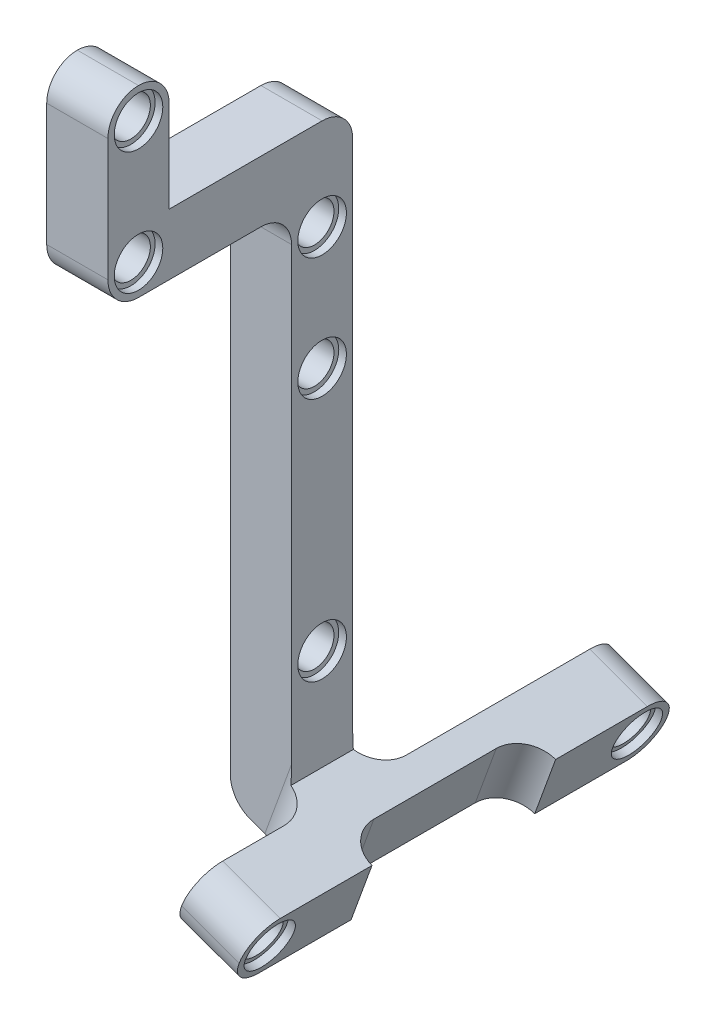
SolidWorks part; units mm, degrees
ref_plane "Front Plane" through (0, 0, 0) normal (1, 0, 0) x (0, 1, 0)
ref_plane "Top Plane" through (0, 0, 0) normal (0, 0, 1) x (0, 1, 0)
ref_plane "Right Plane" through (0, 0, 0) normal (0, 1, 0) x (-1, 0, 0)
sketch "Sketch1" plane through (0, 0, 0) normal (1, 0, 0) x (0, 1, 0)
  line L0 (72, 0) -> (72, 24)
  line L1 (0, 0) -> (72, 0)
  line L2 (0, 0) -> (0, 32)
  line L3 (0, 32) -> (64, 32)
  line L5 (0, 32) -> (64, 32)
  line L6 (0, 32) -> (0, 8)
  line L7 (0, 8) -> (64, 8)
  line L8 (64, 32) -> (64, 8)
  line L9 (64, 32) -> (88, 32)
  line L11 (72, 24) -> (88, 24)
  line L12 (88, 32) -> (88, 24)
  circle A4 centre (68, 28) radius 2.55
  circle A6 centre (84, 28) radius 2.55
  circle A7 centre (12, 4) radius 2.55
  circle A8 centre (44, 4) radius 2.55
  circle A9 centre (60, 4) radius 2.55
  dimension "D5" = 32
  dimension "D14" = 12
  dimension "D15" = 4
  dimension "D16" = 24
  dimension "D17" = 4
  dimension "D19" = 5.1
  dimension "D10" = 5.1
  dimension "D7" = 5.1
  dimension "D9" = 5.1
  dimension "D2" = 8
  dimension "D3" = 24
  dimension "D4" = 64
  dimension "D6" = 16
  dimension "D8" = 32
  dimension "D11" = 16
  dimension "D12" = 4
  dimension "D13" = 4
  dimension "D18" = 8
  dimension "24" = 24
  dimension "D20" = 16
  dimension "D21" = 4
  dimension "D22" = 4
extrude "Boss-Extrude1" add sketch "Sketch1" along normal blind 8 contours L3 L8 L7 L2 L1 region at (0, 36, 0.9364)
sketch "Sketch2" plane through (8, 0, 0) normal (1, 0, 0) x (0, 1, 0)
  circle A0 centre (68, 28) radius 3.175
  circle A7 centre (84, 28) radius 3.175
  circle A8 centre (12, 4) radius 3.175
  circle A9 centre (44, 4) radius 3.175
  circle A10 centre (60, 4) radius 3.175
  dimension "D1" = 6.35
extrude "Cut-Extrude1" cut sketch "Sketch2" against normal blind 1
sketch "Sketch3" plane through (0, 0, 0) normal (-1, 0, 0) x (0, -1, 0)
  circle A3 centre (-12, 4) radius 3.175
  circle A5 centre (-12, 4) radius 3.175
  circle A7 centre (-84, 28) radius 3.175
  circle A23 centre (-84, 28) radius 3.175
  circle A28 centre (-68, 28) radius 3.175
  circle A29 centre (-68, 28) radius 3.175
  circle A40 centre (-60, 4) radius 3.175
  circle A41 centre (-60, 4) radius 3.175
  circle A42 centre (-44, 4) radius 3.175
  circle A43 centre (-44, 4) radius 3.175
  dimension "D5" = 0
  dimension "D1" = 0
  dimension "D2" = 0
  dimension "D11" = 0
  dimension "D12" = 0
extrude "Cut-Extrude2" cut sketch "Sketch3" against normal blind 1
sketch "Sketch4" plane through (0, 0, 8) normal (0, 0, 1) x (1, 0, 0)
  line L0 (8, 0) -> (0, 0) construction
  line L1 (8, 0) -> (8, 64) construction
  line L2 (0, 0) -> (0, -4)
  line L3 (0, 0) -> (0, 64) construction
  line L4 (15.7876, -12.5471) -> (18.5238, -5.0295)
  line L5 (8, -1.1992) -> (18.5238, -5.0295)
  line L6 (15.7876, -12.5471) -> (2.6319, -7.7588)
  line L7 (8, 0) -> (8, -1.1992)
  line L8 (0, 0) -> (8, 0)
  arc A0 (0, -4) -> (2.6319, -7.7588) centre (4, -4) ccw
  dimension "D3" = 8
  dimension "D1" = 4
  dimension "D2" = 4
  dimension "D4" = 8
  dimension "D5" = 14
  dimension "D6" = 110
extrude "Boss-Extrude2" add sketch "Sketch4" against normal blind 8
sketch "Sketch5" plane through (0.5504, 1.5123, 0) normal (0.342, 0.9397, 0) x (-0.9397, 0.342, 0)
  line L0 (-19.1269, 0) -> (-19.1269, 8) construction
  line L1 (-11.1269, -32) -> (-19.1269, -32)
  line L2 (-11.1269, -32) -> (-11.1269, 24)
  line L3 (-11.1269, 24) -> (-19.1269, 24)
  line L4 (-19.1269, -32) -> (-19.1269, 24)
  line L5 (-19.1269, 8) -> (-7.9277, 8) construction
  dimension "D1" = 8
  dimension "D2" = 16
  dimension "D3" = 56
extrude "Boss-Extrude3" add sketch "Sketch5" against normal blind 8
sketch "Sketch6" plane through (0.5504, 1.5123, 0) normal (0.342, 0.9397, 0) x (-0.9397, 0.342, 0)
  line L0 (-19.1269, -32) -> (-19.1269, 24) construction
  line L1 (-19.1269, 8) -> (-15.1269, 8)
  line L2 (-19.1269, 8) -> (-19.1269, -16)
  line L3 (-19.1269, -16) -> (-15.1269, -16)
  line L4 (-15.1269, 8) -> (-15.1269, -16)
  line L5 (-11.1269, 24) -> (-19.1269, 24) construction
  line L6 (-19.1269, -32) -> (-11.1269, -32) construction
  dimension "D1" = 4
  dimension "D2" = 16
  dimension "D3" = 16
extrude "Cut-Extrude3" cut sketch "Sketch6" against normal blind 8
fillet "Fillet2" radius 4 8 edges at (12.0288, -11.179, -32) (14.765, -3.6614, -32) (12.0288, -11.179, 24) (14.765, -3.6614, 24) (9.6382, -6.0521, 0) (9.6382, -6.0521, 8) (13.3969, -7.4202, -16) (13.3969, -7.4202, 8)
sketch "Sketch7" plane through (17.9734, -6.5418, 0) normal (0.9397, -0.342, 0) x (0.342, 0.9397, 0)
  circle A0 centre (-2.3907, 20) radius 2.55
  circle A1 centre (-2.3907, -28) radius 2.55
  dimension "D1" = 5.1
extrude "Cut-Extrude4" cut sketch "Sketch7" against normal blind 8
sketch "Sketch8" plane through (17.9734, -6.5418, 0) normal (0.9397, -0.342, 0) x (0.342, 0.9397, 0)
  circle A0 centre (-2.3907, 20) radius 3.175
  circle A1 centre (-2.3907, -28) radius 3.175
  dimension "D1" = 6.35
  dimension "D2" = 6.35
extrude "Cut-Extrude5" cut sketch "Sketch8" against normal blind 1
sketch "Sketch9" plane through (10.4558, -3.8056, 0) normal (-0.9397, 0.342, 0) x (-0.342, -0.9397, 0)
  circle A1 centre (2.3907, -28) radius 3.175
  circle A2 centre (2.3907, -28) radius 3.175
  circle A3 centre (2.3907, 20) radius 3.175
  circle A4 centre (2.3907, 20) radius 3.175
  dimension "D1" = 0
  dimension "D2" = 0
extrude "Cut-Extrude6" cut sketch "Sketch9" against normal blind 1
fillet "Fillet3" radius 4 2 edges at (4, 64, 8) (4, 72, 0)
fillet "Fillet5" radius 4 3 edges at (4, 88, 24) (4, 64, 32) (4, 88, 32)
